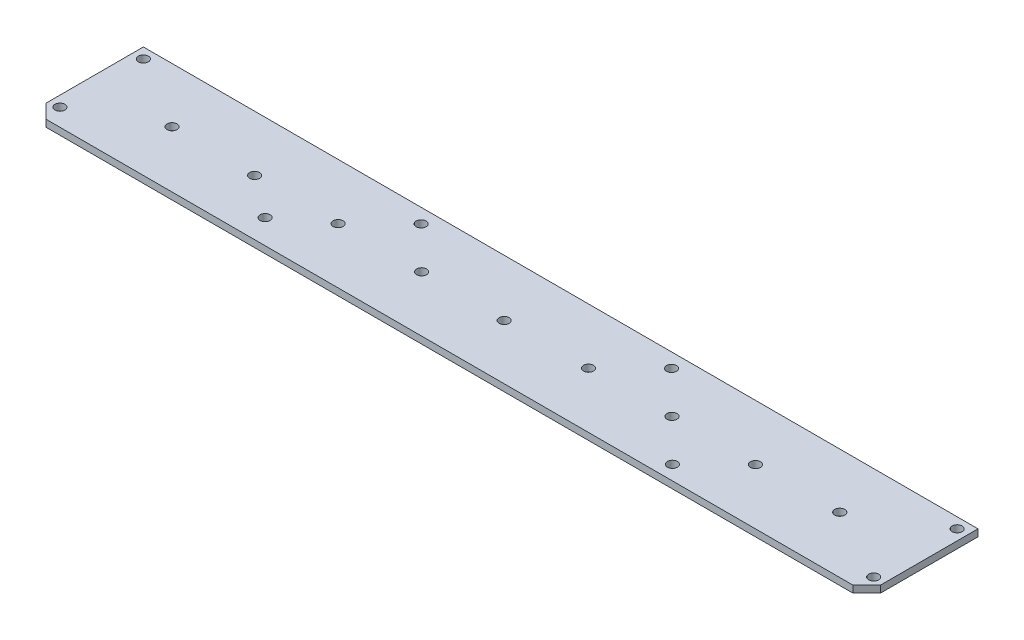
SolidWorks part; units mm, degrees
ref_plane "Front Plane" through (0, 0, 0) normal (0, 0, 1) x (1, 0, 0)
ref_plane "Top Plane" through (0, 0, 0) normal (0, 1, 0) x (1, 0, 0)
ref_plane "Right Plane" through (0, 0, 0) normal (1, 0, 0) x (0, 0, -1)
sketch "Sketch2" plane through (0, 0, 0) normal (0, 1, 0) x (1, 0, 0)
  line L0 (0, 0) -> (0, 50.8)
  line L1 (0, 50.8) -> (381, 50.8)
  line L2 (381, 50.8) -> (381, 0)
  line L3 (381, 0) -> (0, 0)
  dimension "D1" = 50.8
  dimension "D2" = 381
extrude "Boss-Extrude1" add sketch "Sketch2" along normal blind 3.175
sketch "Sketch3" plane through (0, 3.175, 0) normal (0, 1, 0) x (1, 0, 0)
  line L0 (190.5, 0) -> (190.5, 50.8) construction
  line L1 (0, 0) -> (381, 0) construction
  line L2 (381, 50.8) -> (0, 50.8) construction
  line L3 (38.1, 25.7969) -> (190.5, 25.0031) construction
  line L4 (342.9, 25.7969) -> (190.5, 25.0031) construction
  line L5 (0, 6.35) -> (6.35, 0)
  line L6 (6.35, 0) -> (0, 0)
  line L7 (0, 0) -> (0, 6.35)
  line L8 (374.65, 0) -> (381, 0)
  line L9 (381, 6.35) -> (374.65, 0)
  line L10 (381, 0) -> (381, 6.35)
  line L11 (247.65, 44.2526) -> (285.75, 6.5474) construction
  line L12 (0, 50.8) -> (0, 0) construction
  circle A0 centre (190.5, 25.0031) radius 2.286
  circle A1 centre (38.1, 25.7969) radius 2.286
  circle A2 centre (114.3, 25.4) radius 2.286
  circle A3 centre (76.2, 25.4) radius 2.286
  circle A4 centre (152.4, 25.4) radius 2.286
  circle A5 centre (228.6, 25.4) radius 2.286
  circle A6 centre (304.8, 25.4) radius 2.286
  circle A7 centre (266.7, 25.4) radius 2.286
  circle A8 centre (342.9, 25.7969) radius 2.286
  circle A9 centre (247.65, 44.2526) radius 2.286
  circle A10 centre (285.75, 6.5474) radius 2.286
  circle A12 centre (133.35, 44.2526) radius 2.286
  circle A13 centre (4.7625, 46.0375) radius 2.286
  circle A14 centre (4.7625, 7.9375) radius 2.286
  circle A15 centre (376.2375, 7.9375) radius 2.286
  circle A16 centre (376.2375, 46.0375) radius 2.286
  circle A18 centre (95.25, 11.1125) radius 2.286
  point P37 (266.7, 25.4)
  point P52 (0, 0)
  dimension "D1" = 4.572
  dimension "D2" = 0.7937
  dimension "D6" = 25.4
  dimension "D11" = 4.7625
  dimension "D14" = 4.572
  dimension "D15" = 95.25
  dimension "D16" = 4.572
  dimension "D3" = 152.4
  dimension "D4" = 38.1
  dimension "D5" = 38.1
  dimension "D7" = 6.35
  dimension "D8" = 6.35
  dimension "D9" = 45
  dimension "D10" = 19.05
  dimension "D12" = 4.7625
  dimension "D13" = 7.9375
  dimension "D17" = 11.1125
extrude "Cut-Extrude1" cut sketch "Sketch3" against normal up to next
